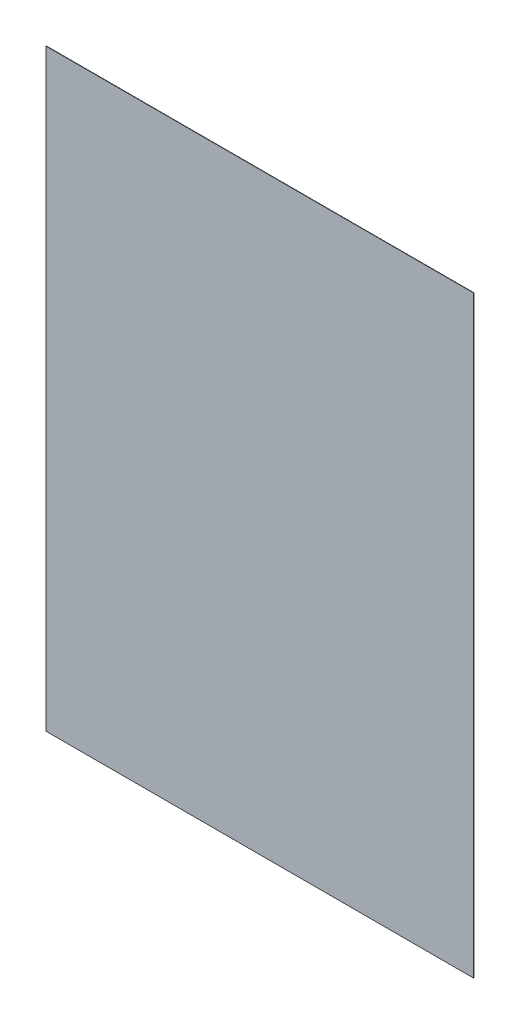
SolidWorks part; units mm, degrees
ref_plane "Front Plane" through (0, 0, 0) normal (0, 0, 1) x (1, 0, 0)
ref_plane "Top Plane" through (0, 0, 0) normal (0, 1, 0) x (1, 0, 0)
ref_plane "Right Plane" through (0, 0, 0) normal (1, 0, 0) x (0, 0, -1)
sketch "Sketch1" plane through (0, 0, 0) normal (0, 0, 1) x (1, 0, 0)
  line L1 (0, 0) -> (1170, 0)
  line L2 (0, 0) -> (0, 1625)
  line L3 (0, 1625) -> (1170, 1625)
  line L4 (1170, 0) -> (1170, 1625)
  dimension "D1" = 1170
  dimension "D2" = 1625
extrude "Boss-Extrude1" add sketch "Sketch1" along normal blind 1
